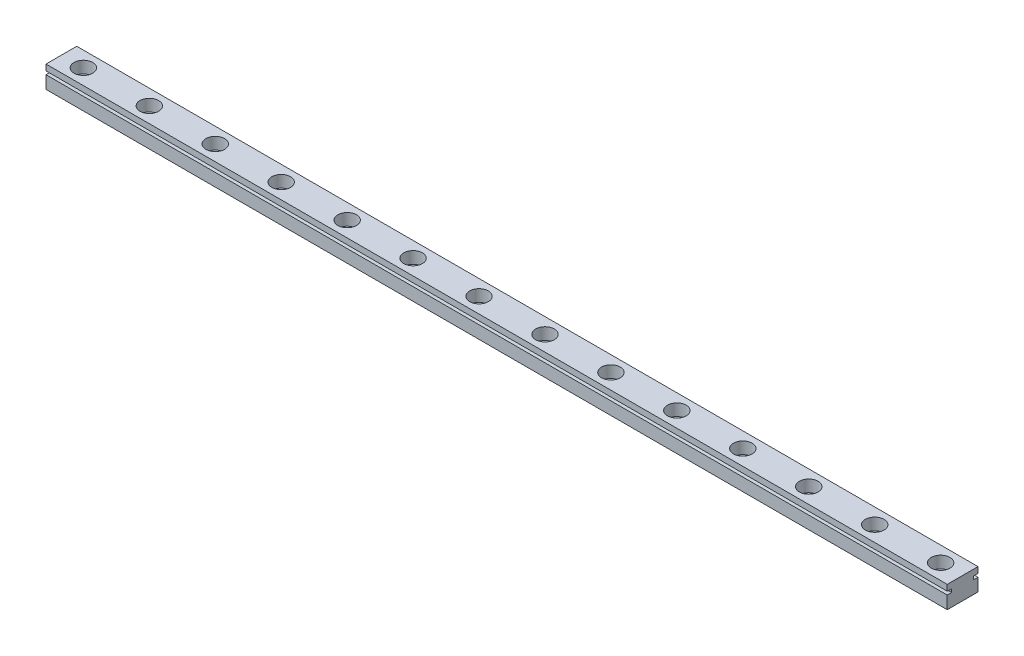
SolidWorks part; units mm, degrees
material "普通碳钢"
ref_plane "前视基准面" through (0, 0, 0) normal (0, 0, 1) x (1, 0, 0)
ref_plane "上视基准面" through (0, 0, 0) normal (0, 1, 0) x (1, 0, 0)
ref_plane "右视基准面" through (0, 0, 0) normal (1, 0, 0) x (0, 0, -1)
sketch "草图2" plane through (0, 0, 0) normal (1, 0, 0) x (0, 0, -1)
  line L0 (3.5, 1.15) -> (2.5, 1.15)
  line L1 (-3.5, 2.5) -> (3.5, 2.5)
  line L2 (-3.5, 2.5) -> (-3.5, -2.5)
  line L3 (-3.5, -2.5) -> (3.5, -2.5)
  line L4 (3.5, 2.5) -> (3.5, -2.5)
  line L5 (2.5, 1.15) -> (2.5, 0.4)
  line L6 (2.5, 0.4) -> (3.5, 0.4)
  line L7 (0, 55) -> (0, -55) construction
  line L8 (-2.5, 0.4) -> (-3.5, 0.4)
  line L9 (-2.5, 1.15) -> (-2.5, 0.4)
  line L10 (-3.5, 1.15) -> (-2.5, 1.15)
  dimension "D1" = 5
  dimension "D2" = 7
  dimension "D3" = 2.5
  dimension "D4" = 3.5
  dimension "D5" = 1.35
  dimension "D6" = 0.75
  dimension "D7" = 1
extrude "凸台-拉伸1" add sketch "草图2" along normal blind 205 contours L2 L10 L9 L8 L3 L4 L6 L5 L0 L1 region at (0, -0.0347, 0)
sketch "草图3" plane through (0, 0, 0) normal (0, 1, 0) x (1, 0, 0)
  circle A0 centre (5, 0) radius 2.125
  circle A1 centre (5, 0) radius 1
  dimension "D1" = 2
  dimension "D2" = 4.25
  dimension "D3" = 5
extrude "切除-拉伸1" cut sketch "草图3" along normal blind 25 and the other way blind 25 contours A1 region at (5, 0, 0)
extrude "切除-拉伸2" cut sketch "草图3<3>" against normal blind 2.7 from surface contours A0 A1 region at (2.9351, 0, 0) starting at face at (5, 2.5, 1)
sketch "草图3<3>" plane through (0, 0, 0) normal (0, 1, 0) x (1, 0, 0) same geometry as "草图3"
pattern_linear "阵列(线性)1" count 14 spacing 15 along (1, 0, 0) of "切除-拉伸1", "切除-拉伸2"
